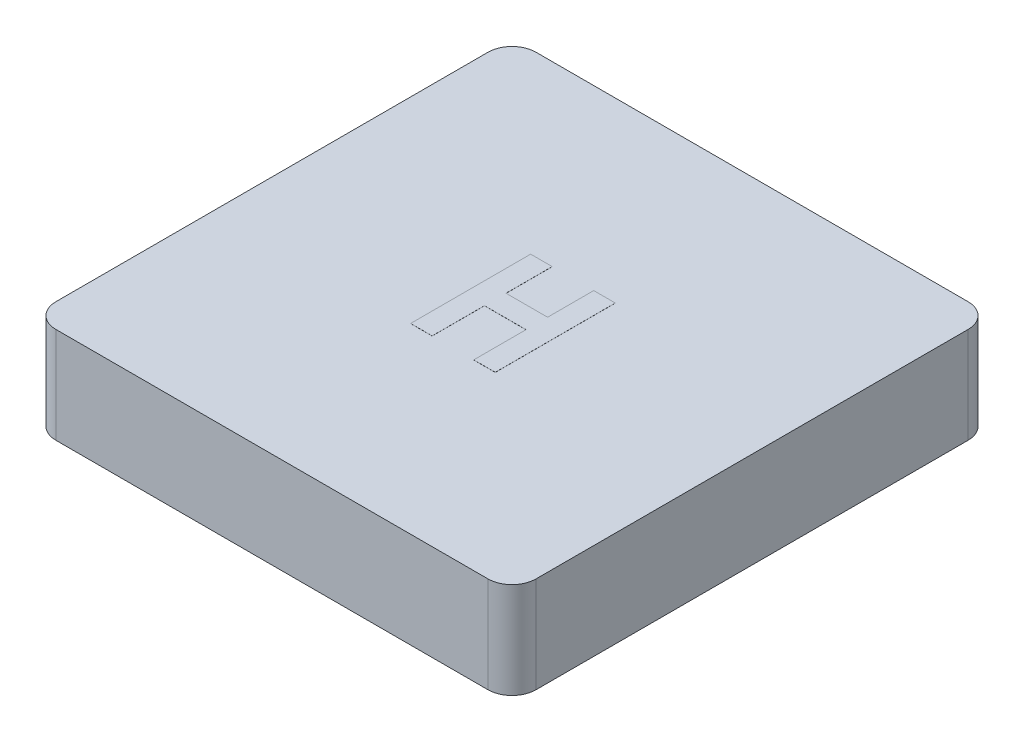
SolidWorks part; units mm, degrees
ref_plane "Front Plane" through (0, 0, 0) normal (0, 0, 1) x (1, 0, 0)
ref_plane "Top Plane" through (0, 0, 0) normal (0, 1, 0) x (1, 0, 0)
ref_plane "Right Plane" through (0, 0, 0) normal (1, 0, 0) x (0, 0, -1)
sketch "Sketch1" plane through (0, 0, 0) normal (0, 1, 0) x (1, 0, 0)
  line L0 (0, 0) -> (12.7, 0)
  line L1 (12.7, 0) -> (12.7, 12.7)
  line L2 (12.7, 12.7) -> (0, 12.7)
  line L3 (0, 12.7) -> (0, 0)
  dimension "D1" = 12.7
  dimension "D2" = 12.7
extrude "Boss-Extrude1" add sketch "Sketch1" along normal blind 2.54
fillet "Fillet1" radius 0.635 4 edges at (0, 1.27, -12.7) (12.7, 1.27, -12.7) (12.7, 1.27, 0) (0, 1.27, 0)
shell "Shell1" thickness 0.635 removed face at (6.35, 0, -6.35)
sketch "Sketch2" plane through (0, 1.905, 0) normal (0, -1, 0) x (-1, 0, 0)
  line L0 (-0.635, 6.35) -> (-12.065, 6.35) construction
  line L1 (-0.635, 12.065) -> (-0.635, 0.635) construction
  line L2 (-12.065, 0.635) -> (-12.065, 12.065) construction
  line L3 (-6.35, 0.635) -> (-6.35, 12.065) construction
  line L4 (-0.635, 0.635) -> (-12.065, 0.635) construction
  line L5 (-12.065, 12.065) -> (-0.635, 12.065) construction
  circle A0 centre (-6.35, 6.35) radius 2.54
  dimension "D1" = 5.08
extrude "Boss-Extrude2" add sketch "Sketch2" along normal up to surface (1.905 mm away) up to face at (6.35, 0, -6.35)
sketch "Sketch3" plane through (0, 2.54, 0) normal (0, 1, 0) x (1, 0, 0)
  line L0 (0, 12.065) -> (0, 0.635) construction
  line L1 (0.635, 0) -> (12.065, 0) construction
  text T0 "<b>H</b>"
  point P1 (0, 0)
  dimension "D1" = 4.826
  dimension "D2" = 4.826
extrude "Boss-Extrude3" add sketch "Sketch3" along normal blind 0.0025
